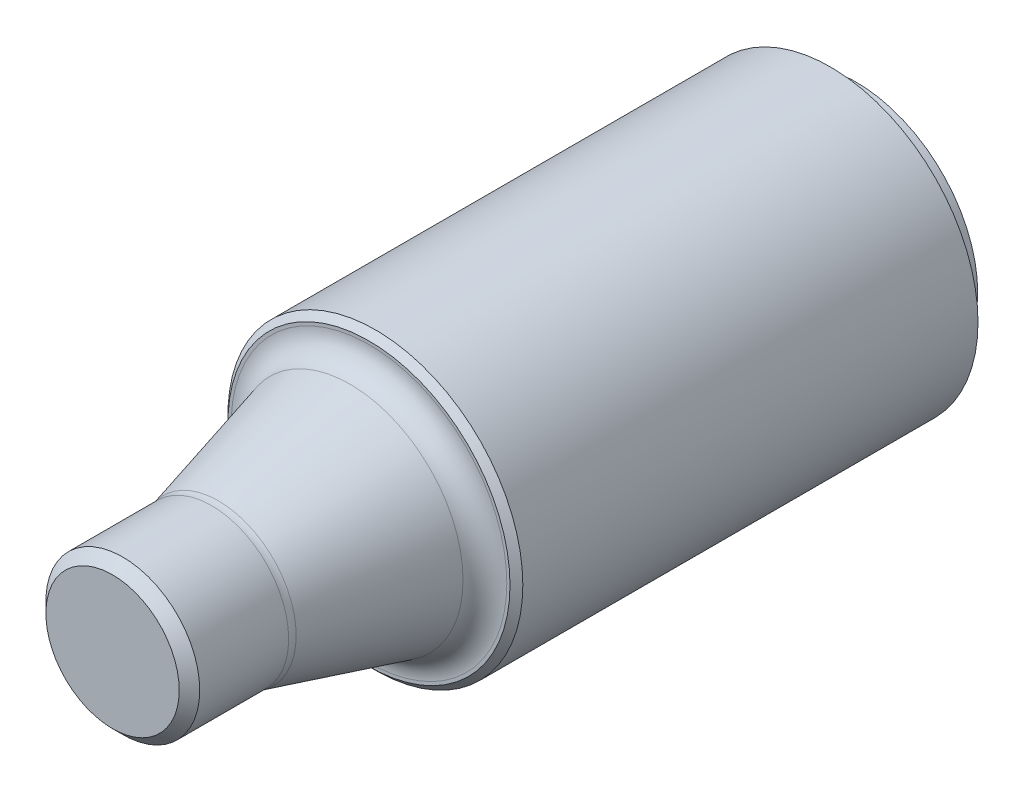
SolidWorks part; units mm, degrees
material "PET"
ref_plane "Front Plane" through (0, 0, 0) normal (0, 0, 1) x (1, 0, 0)
ref_plane "Top Plane" through (0, 0, 0) normal (0, 1, 0) x (1, 0, 0)
ref_plane "Right Plane" through (0, 0, 0) normal (1, 0, 0) x (0, 0, -1)
sketch "Sketch1" plane through (0, 0, 0) normal (0, 0, 1) x (1, 0, 0)
  circle A2 centre (0, 0) radius 30.0863
  circle A3 centre (0, 0) radius 30.0863
  dimension "D1" = 1.27
extrude "Boss-Extrude1" add sketch "Sketch1" against normal blind 95.25
sketch "Sketch2" plane through (0, 0, 0) normal (0, 0, 1) x (1, 0, 0)
  circle A0 centre (0, 0) radius 36.5125 construction
  circle A1 centre (0, 0) radius 36.5125
extrude "Boss-Extrude2" add sketch "Sketch2" along normal blind 25.4 and the other way offset from surface 6.35 other way up to face at (30.0863, 0, -95.25)
sketch "Sketch3" plane through (0, 0, 25.4) normal (0, 0, 1) x (1, 0, 0)
  circle A0 centre (0, 0) radius 19.05
  dimension "D1" = 38.1
extrude "Boss-Extrude3" add sketch "Sketch3" along normal blind 38.1
draft "Draft1" type of draft neutral plane draft angle 15 faces to draft 1 face at (19.05, 0, 63.5) neutral plane through (0, 0, 63.5) neutral plane normal (0, 0, 1) parameters "D1"=15
sketch "Sketch4" plane through (0, 0, 63.5) normal (0, 0, 1) x (1, 0, 0)
  circle A1 centre (0, 0) radius 19.05
  circle A2 centre (0, 0) radius 19.05
  dimension "D1" = 0
extrude "Boss-Extrude4" add sketch "Sketch4" along normal blind 25.4
chamfer "Chamfer1" distance 2.54 angle 45 1 edges at (19.05, 0, 88.9)
fillet "Fillet1" radius 6.35 2 edges at (29.2589, 0, 25.4) (19.05, 0, 63.5)
chamfer "Chamfer2" distance 1.5875 angle 45 1 edges at (36.5125, 0, 25.4)
sketch "Sketch5" plane through (0, 0, -95.25) normal (0, 0, -1) x (-1, 0, 0)
  circle A0 centre (0, 0) radius 26.9113
  circle A1 centre (0, 0) radius 30.0863 construction
  dimension "D1" = 3.175
extrude "Cut-Extrude1" cut sketch "Sketch5" against normal up to surface (120.65 mm away) up to face at (34.925, 0, 25.4)
sketch "Sketch6" plane through (0, 0, 25.4) normal (0, 0, -1) x (-1, 0, 0)
  circle A0 centre (0, 0) radius 15.875
  circle A1 centre (0, 0) radius 19.05 construction
  circle A2 centre (0, 0) radius 16.51 construction
  dimension "D1" = 3.175
extrude "Cut-Extrude2" cut sketch "Sketch6" against normal offset from surface (60.325 mm away) 3.175 up to face at (16.51, 0, 88.9)
sketch "Sketch9" plane through (0, 0, -95.25) normal (0, 0, -1) x (-1, 0, 0)
  line L0 (-17.3073, -1.0596) -> (-37.8448, 0.9697)
  line L1 (-37.8448, 0.9697) -> (-33.9423, 40.4648)
  line L2 (-33.9423, 40.4648) -> (-13.4048, 38.4355)
  line L3 (-13.4048, 38.4355) -> (-17.3073, -1.0596)
extrude "Cut-Extrude3" [suppressed] cut sketch "Sketch9" against normal blind 61.595
